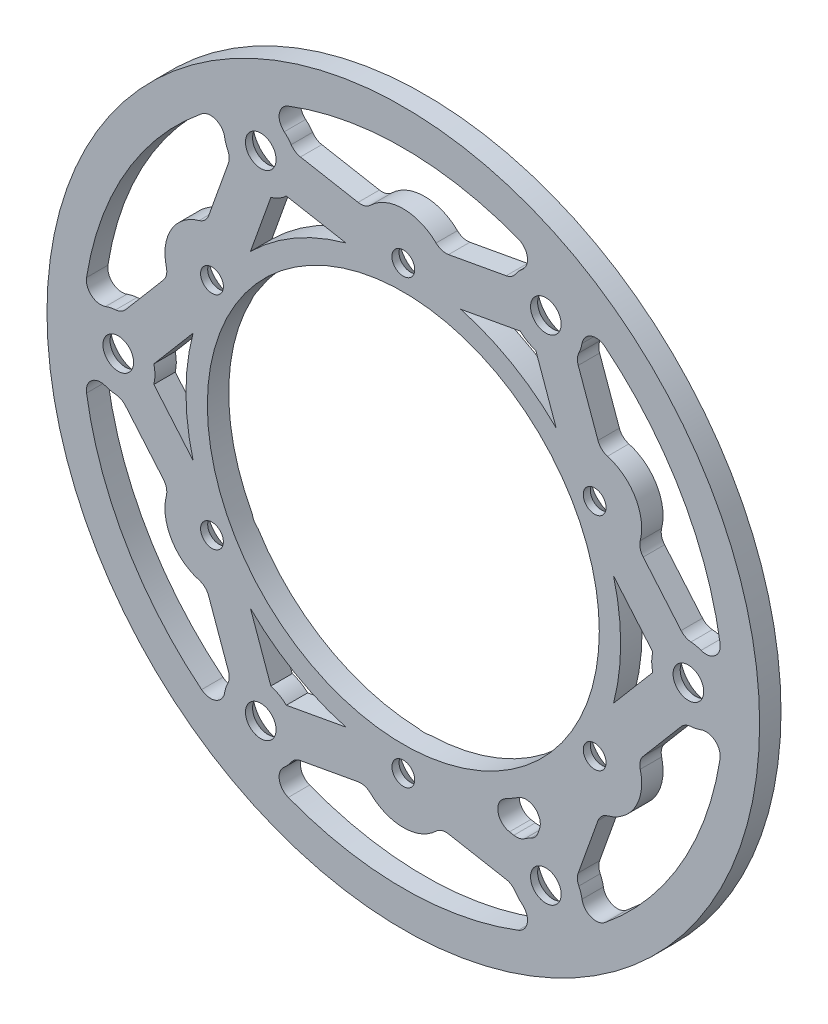
SolidWorks part; units mm, degrees
material "Thornel Mat VMA"
ref_plane "前视基准面" through (0, 0, 0) normal (0, 0, 1) x (1, 0, 0)
ref_plane "上视基准面" through (0, 0, 0) normal (0, 1, 0) x (1, 0, 0)
ref_plane "右视基准面" through (0, 0, 0) normal (1, 0, 0) x (0, 0, -1)
other "Configuration Table"
sketch "草图1" plane through (0, 0, 0) normal (0, 0, 1) x (1, 0, 0)
  line L0 (0, 0) -> (0, 39856.214) construction
  line L1 (0, 0) -> (39856.214, 0) construction
  line L2 (-4.8, 49.7691) -> (-4.8, 38.7035)
  line L3 (4.8, 49.7691) -> (4.8, 38.7035)
  line L4 (40.7013, 29.0415) -> (31.1182, 23.5087)
  line L5 (45.5013, 20.7276) -> (35.9182, 15.1948)
  line L6 (45.5013, -20.7276) -> (35.9182, -15.1948)
  line L7 (40.7013, -29.0415) -> (31.1182, -23.5087)
  line L8 (4.8, -49.7691) -> (4.8, -38.7035)
  line L9 (-4.8, -49.7691) -> (-4.8, -38.7035)
  line L10 (-40.7013, -29.0415) -> (-31.1182, -23.5087)
  line L11 (-45.5013, -20.7276) -> (-35.9182, -15.1948)
  line L12 (-45.5013, 20.7276) -> (-35.9182, 15.1948)
  line L13 (-40.7013, 29.0415) -> (-31.1182, 23.5087)
  circle A0 centre (0, 0) radius 50
  circle A1 centre (0, 0) radius 39
  circle A2 centre (0, 41.5) radius 2.5
  circle A3 centre (0, 0) radius 41.5 construction
  circle A4 centre (35.9401, 20.75) radius 2.5
  circle A5 centre (35.9401, -20.75) radius 2.5
  circle A6 centre (0, -41.5) radius 2.5
  circle A7 centre (-35.9401, -20.75) radius 2.5
  circle A8 centre (-35.9401, 20.75) radius 2.5
  point P27 (0, 0)
  point P48 (0, 0)
  dimension "D1" = 100
  dimension "D2" = 78
  dimension "D5" = 5
  dimension "D6" = 83
  dimension "D3" = 4.8
  dimension "D4" = 6
  dimension "D7" = 6
extrude "凸台-拉伸2" add sketch "草图1" along normal blind 3 contours A8 | A1 A8 L13 A0 L12 | A1 L2 A0 L13 | A2 | A1 A2 L3 A0 L2 | A1 L4 A0 L3 | A4 | A1 A4 L5 A0 L4 | A1 L6 A0 L5 | A5 | A1 A5 L7 A0 L6 | A1 L8 A0 L7 | A6 | A1 A6 L9 A0 L8 | A1 L10 A0 L9 | A7 | A1 A7 L11 A0 L10 | A1 L12 A0 L11 | A1 | A0 region at (0, 41.5, 0) region at (0, 45.0756, 0) region at (-21.7517, 37.6751, 0) region at (0, 0, 0) region at (21.7517, 37.6751, 0) region at (-35.9401, 20.75, 0) region at (-39.0366, 22.5378, 0) region at (35.9401, 20.75, 0) region at (39.0366, 22.5378, 0) region at (-43.5034, 0, 0) region at (43.5034, 0, 0) region at (-35.9401, -20.75, 0) region at (-39.0366, -22.5378, 0) region at (-21.7517, -37.6751, 0) region at (35.9401, -20.75, 0) region at (39.0366, -22.5378, 0) region at (0, -41.5, 0) region at (0, -45.0756, 0) region at (21.7517, -37.6751, 0)
sketch "草图2" plane through (0, 0, 3) normal (0, 0, 1) x (1, 0, 0)
  circle A0 centre (0, 0) radius 27.5
  dimension "D1" = 55
extrude "切除-拉伸1" cut sketch "草图2" against normal blind 4
sketch "草图3" plane through (0, 0, 3) normal (0, 0, 1) x (1, 0, 0)
  line L0 (0, 0) -> (0, 50000) construction
  circle A0 centre (0, 0) radius 31 construction
  circle A1 centre (0, 31) radius 1.6
  circle A2 centre (26.8468, 15.5) radius 1.6
  circle A3 centre (26.8468, -15.5) radius 1.6
  circle A4 centre (0, -31) radius 1.6
  circle A5 centre (-26.8468, -15.5) radius 1.6
  circle A6 centre (-26.8468, 15.5) radius 1.6
  point P19 (0, 0)
  dimension "D1" = 62
  dimension "D2" = 3.2
  dimension "D3" = 6
extrude "切除-拉伸2" cut sketch "草图3" against normal blind 4
fillet "圆角1" [suppressed] radius 3
fillet "圆角2" [suppressed] radius 1
chamfer "倒角1" distance 2 angle 45 6 edges at (1.6, 31, 0) (28.4468, 15.5, 0) (28.4468, -15.5, 0) (1.6, -31, 0) (-25.2468, -15.5, 0) (-25.2468, 15.5, 0)
sketch "草图4" plane through (0, 0, 0) normal (0, 0, -1) x (-1, 0, 0)
  line L0 (0, 0) -> (50000, 0) construction
  line L1 (0, 0) -> (0, -50000) construction
  line L2 (21.25, 36.8061) -> (-24978.75, -43264.4641) construction
  circle A0 centre (0, 0) radius 40 construction
  circle A1 centre (20, 34.641) radius 2.15
  dimension "D1" = 80
  dimension "D2" = 4.3
  dimension "D3" = 30
extrude "切除-拉伸3" cut sketch "草图4" against normal through all both and the other way through all
pattern_circular "阵列(圆周)1" count 6 over 360 about axis through (0, 0, 3) along (0, 0, -1) of "切除-拉伸3" reverse direction yes
sketch "草图5" plane through (0, 0, 0) normal (0, 0, -1) x (-1, 0, 0)
  line L0 (-40, 0) -> (-26.8468, 15.5) construction
  line L1 (-26.8468, 15.5) -> (-20, 34.641) construction
  line L2 (-20, 34.641) -> (0, 31) construction
  line L3 (0, 31) -> (20, 34.641) construction
  line L4 (20, 34.641) -> (26.8468, 15.5) construction
  line L5 (26.8468, 15.5) -> (40, 0) construction
  line L6 (40, 0) -> (26.8468, -15.5) construction
  line L7 (26.8468, -15.5) -> (20, -34.641) construction
  line L8 (20, -34.641) -> (0, -31) construction
  line L9 (0, -31) -> (-20, -34.641) construction
  line L10 (-20, -34.641) -> (-26.8468, -15.5) construction
  line L11 (-26.8468, -15.5) -> (-40, 0) construction
  line L12 (-29.4876, -17.0247) -> (-43.9346, 0)
  line L13 (-43.9346, 0) -> (-29.4876, 17.0247)
  line L14 (-29.4876, 17.0247) -> (-21.9673, 38.0485)
  line L15 (-21.9673, 38.0485) -> (0, 34.0493)
  line L16 (0, 34.0493) -> (21.9673, 38.0485)
  line L17 (21.9673, 38.0485) -> (29.4876, 17.0247)
  line L18 (29.4876, 17.0247) -> (43.9346, 0)
  line L19 (43.9346, 0) -> (29.4876, -17.0247)
  line L20 (29.4876, -17.0247) -> (21.9673, -38.0485)
  line L21 (21.9673, -38.0485) -> (0, -34.0493)
  line L22 (0, -34.0493) -> (-21.9673, -38.0485)
  line L23 (-21.9673, -38.0485) -> (-29.4876, -17.0247)
  line L24 (-24.206, -13.9753) -> (-36.0654, 0)
  line L25 (-36.0654, 0) -> (-24.206, 13.9753)
  line L26 (-24.206, 13.9753) -> (-18.0327, 31.2336)
  line L27 (-18.0327, 31.2336) -> (0, 27.9507)
  line L28 (0, 27.9507) -> (18.0327, 31.2336)
  line L29 (18.0327, 31.2336) -> (24.206, 13.9753)
  line L30 (24.206, 13.9753) -> (36.0654, 0)
  line L31 (36.0654, 0) -> (24.206, -13.9753)
  line L32 (24.206, -13.9753) -> (18.0327, -31.2336)
  line L33 (18.0327, -31.2336) -> (0, -27.9507)
  line L34 (0, -27.9507) -> (-18.0327, -31.2336)
  line L35 (-18.0327, -31.2336) -> (-24.206, -13.9753)
  circle A0 centre (-20, 34.641) radius 5.15
  circle A1 centre (20, 34.641) radius 2.15
  circle A2 centre (20, 34.641) radius 2.15 construction
  circle A3 centre (-20, 34.641) radius 2.15
  circle A4 centre (-20, 34.641) radius 2.15 construction
  circle A5 centre (-40, 0) radius 2.15
  circle A6 centre (-40, 0) radius 2.15 construction
  circle A7 centre (-20, -34.641) radius 2.15
  circle A8 centre (-20, -34.641) radius 2.15 construction
  circle A9 centre (20, -34.641) radius 2.15
  circle A10 centre (20, -34.641) radius 2.15 construction
  circle A11 centre (40, 0) radius 2.15
  arc A12 (-0.7935, 27.4885) -> (-23.409, 14.4315) centre (0, 0) ccw
  arc A24 (-0.7935, 27.4885) -> (-23.409, 14.4315) centre (0, 0) ccw construction
  circle A36 centre (40, 0) radius 2.15 construction
  arc A37 (1.4548, 24.5623) -> (-1.4548, 24.5623) centre (0, 31) ccw
  circle A38 centre (20, 34.641) radius 5.15
  arc A39 (21.999, 11.0213) -> (20.5442, 13.5411) centre (26.8468, 15.5) ccw
  circle A40 centre (40, 0) radius 5.15
  arc A41 (20.5442, -13.5411) -> (21.999, -11.0213) centre (26.8468, -15.5) ccw
  arc A42 (-1.4548, -24.5623) -> (1.4548, -24.5623) centre (0, -31) ccw
  arc A43 (-21.999, -11.0213) -> (-20.5442, -13.5411) centre (-26.8468, -15.5) ccw
  arc A44 (-20.5442, 13.5411) -> (-21.999, 11.0213) centre (-26.8468, 15.5) ccw
  circle A45 centre (-40, 0) radius 5.15
  circle A46 centre (-20, -34.641) radius 5.15
  circle A47 centre (20, -34.641) radius 5.15
  circle A48 centre (-26.8468, 15.5) radius 1.6 construction
  circle A49 centre (-26.8468, -15.5) radius 1.6 construction
  circle A50 centre (0, 0) radius 30.5
  circle A51 centre (0, 0) radius 30.5
  circle A53 centre (0, 0) radius 45
  circle A54 centre (0, 0) radius 45
  circle A55 centre (0, -31) radius 1.6 construction
  circle A56 centre (26.8468, -15.5) radius 1.6 construction
  circle A57 centre (26.8468, 15.5) radius 1.6 construction
  circle A58 centre (0, 31) radius 1.6 construction
  arc A59 (0.7935, 27.4885) -> (-0.7935, 27.4885) centre (0, 31) ccw
  arc A60 (23.409, 14.4315) -> (0.7935, 27.4885) centre (0, 0) ccw
  arc A61 (23.409, 14.4315) -> (0.7935, 27.4885) centre (0, 0) ccw
  arc A62 (24.2026, 13.057) -> (23.409, 14.4315) centre (26.8468, 15.5) ccw
  arc A63 (24.2026, -13.057) -> (24.2026, 13.057) centre (0, 0) ccw
  arc A64 (24.2026, -13.057) -> (24.2026, 13.057) centre (0, 0) ccw
  arc A65 (23.409, -14.4315) -> (24.2026, -13.057) centre (26.8468, -15.5) ccw
  arc A66 (0.7935, -27.4885) -> (23.409, -14.4315) centre (0, 0) ccw
  arc A67 (0.7935, -27.4885) -> (23.409, -14.4315) centre (0, 0) ccw
  arc A68 (-0.7935, -27.4885) -> (0.7935, -27.4885) centre (0, -31) ccw
  arc A69 (-23.409, -14.4315) -> (-0.7935, -27.4885) centre (0, 0) ccw
  arc A70 (-23.409, -14.4315) -> (-0.7935, -27.4885) centre (0, 0) ccw
  arc A71 (-24.2026, -13.057) -> (-23.409, -14.4315) centre (-26.8468, -15.5) ccw
  arc A72 (-24.2026, 13.057) -> (-24.2026, -13.057) centre (0, 0) ccw
  arc A73 (-24.2026, 13.057) -> (-24.2026, -13.057) centre (0, 0) ccw
  arc A74 (-23.409, 14.4315) -> (-24.2026, 13.057) centre (-26.8468, 15.5) ccw
  dimension "D13" = 5
  dimension "D1" = 0
  dimension "D2" = 0
  dimension "D3" = 0
  dimension "D4" = 0
  dimension "D5" = 0
  dimension "D6" = 0
  dimension "D7" = 0
  dimension "D8" = 3
  dimension "D9" = 3
  dimension "D10" = 3
  dimension "D11" = 3
  dimension "D12" = 5
extrude "切除-拉伸4" cut sketch "草图5" against normal through all both contours A47 A54 A40 L19 A41 L20 | A51 L31 A40 L30 | A40 A54 A38 L17 A39 L18 | A51 L29 A38 L28 | A38 A54 A0 L15 A37 L16 | A0 A54 A45 L13 A44 L14 | A51 L27 A0 L26 | A51 L25 A45 L24 | A45 A54 A46 L23 A43 L12 | A51 L35 A46 L34 | A46 A54 A47 L21 A42 L22 | A51 L33 A47 L32 region at (34.7867, -20.0841, 0) region at (32.0184, 0, 0) region at (16.0092, -27.7288, 0) region at (34.7867, 20.0841, 0) region at (0, -40.1682, 0) region at (0, 40.1682, 0) region at (-34.7867, -20.0841, 0) region at (16.0092, 27.7288, 0) region at (-16.0092, -27.7288, 0) region at (-34.7867, 20.0841, 0) region at (-16.0092, 27.7288, 0) region at (-32.0184, 0, 0)
fillet "圆角3" radius 2 40 edges at (32.9379, -12.9587, 1.5) (27.6915, -22.0457, 1.5) (24.2346, -31.71, 1.5) (23.6238, -38.3004, 1.5) (44.981, -1.3086, 1.5) (39.579, -5.1328, 1.5) (5.2464, -35.0044, 1.5) (-5.2464, -35.0044, 1.5) (-15.3444, -36.8428, 1.5) (-21.3572, -39.609, 1.5) (21.3572, -39.609, 1.5) (15.3444, -36.8428, 1.5) (-27.6915, -22.0457, 1.5) (-32.9379, -12.9587, 1.5) (-39.579, -5.1328, 1.5) (-44.981, -1.3086, 1.5) (-23.6238, -38.3004, 1.5) (-24.2346, -31.71, 1.5) (-32.9379, 12.9587, 1.5) (-27.6915, 22.0457, 1.5) (-24.2346, 31.71, 1.5) (-23.6238, 38.3004, 1.5) (-44.981, 1.3086, 1.5) (-39.579, 5.1328, 1.5) (-5.2464, 35.0044, 1.5) (15.3444, 36.8428, 1.5) (21.3572, 39.609, 1.5) (-21.3572, 39.609, 1.5) (-15.3444, 36.8428, 1.5) (5.2464, 35.0044, 1.5) (27.6915, 22.0457, 1.5) (32.9379, 12.9587, 1.5) (44.981, 1.3086, 1.5) (23.6238, 38.3004, 1.5) (24.2346, 31.71, 1.5) (39.579, 5.1328, 1.5) (16.419, -30.9398, 1.5) (18.5851, -29.6892, 1.5) (8.055, -29.4171, 1.5) (21.4485, -21.6844, 1.5)
chamfer "倒角2" distance 2 angle 45 6 edges at (42.15, 0, 0) (22.15, 34.641, 0) (-17.85, 34.641, 0) (-37.85, 0, 0) (-17.85, -34.641, 0) (22.15, -34.641, 0)
